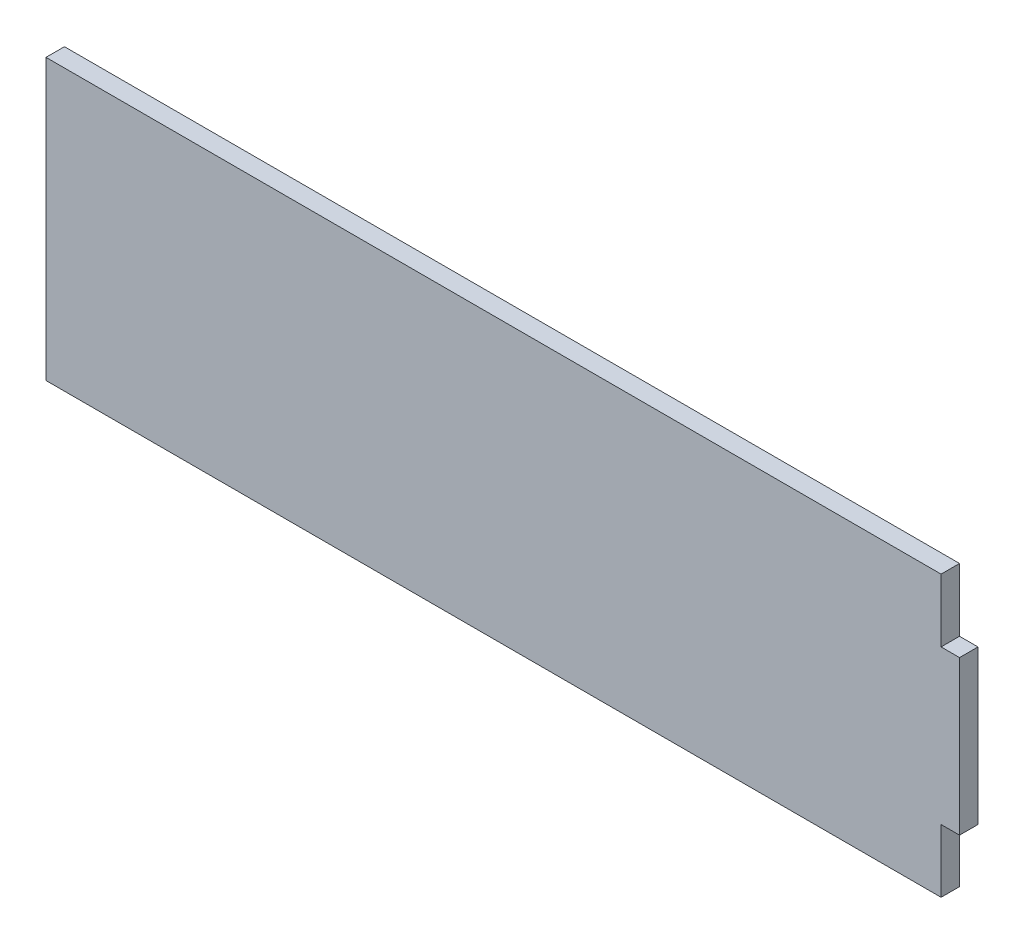
SolidWorks part; units mm, degrees
material "Maple"
ref_plane "Front Plane" through (0, 0, 0) normal (0, 0, 1) x (1, 0, 0)
ref_plane "Top Plane" through (0, 0, 0) normal (0, 1, 0) x (1, 0, 0)
ref_plane "Right Plane" through (0, 0, 0) normal (1, 0, 0) x (0, 0, -1)
sketch "Sketch1" plane through (0, 0, 0) normal (0, 0, 1) x (1, 0, 0)
  line L0 (0, 0) -> (0, -91)
  line L1 (0, 0) -> (291, 0)
  line L3 (0, -91) -> (291, -91)
  line L4 (291, 0) -> (291, -20.5)
  line L6 (291, -70.5) -> (291, -91)
  line L7 (291, -20.5) -> (297, -20.5)
  line L9 (291, -70.5) -> (297, -70.5)
  line L10 (297, -20.5) -> (297, -70.5)
  dimension "D1" = 291
  dimension "D2" = 91
  dimension "D3" = 50
  dimension "D4" = 91
  dimension "D5" = 6
  dimension "D6" = 20.5
  dimension "D7" = 20.5
extrude "Boss-Extrude1" add sketch "Sketch1" along normal blind 6 contours L1 L4 L7 L10 L9 L6 L3 L0
